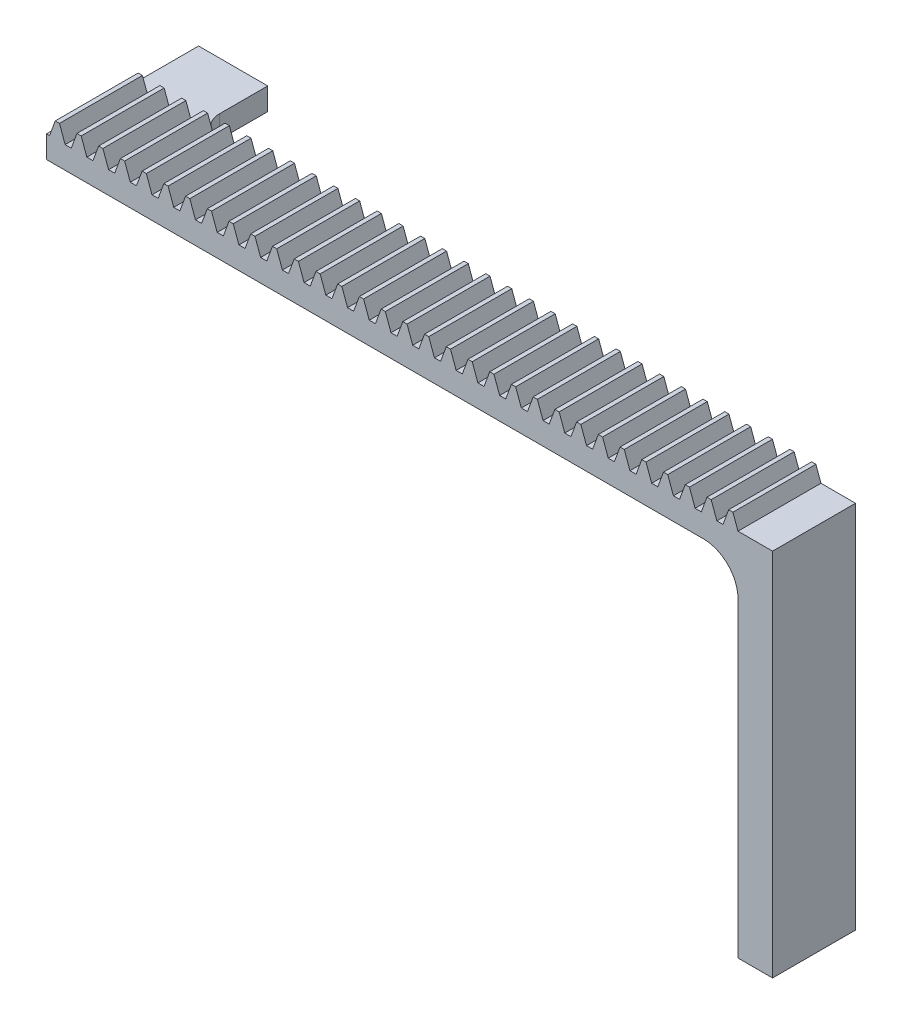
SolidWorks part; units mm, degrees
extrude "Blank" add sketch "BlankSke" against normal blind 12
sketch "BlankSke" plane through (0, 0, 0) normal (0, 0, 1) x (1, 0, 0)
  line L1 (0, 0) -> (100, 0)
  line L2 (0, 0) -> (0, 11)
  line L3 (0, 11) -> (100, 11)
  line L4 (100, 0) -> (100, 11)
  dimension "Length" = 100
ref_plane "Plane1" through (0, 0, 0) normal (0, 0, 1) x (1, 0, 0)
ref_plane "Plane2" through (0, 0, 0) normal (0, 1, 0) x (1, 0, 0)
ref_plane "Plane3" through (0, 0, 0) normal (1, 0, 0) x (0, 0, -1)
sketch "HoldingSke" plane through (0, 0, 0) normal (0, 1, 0) x (1, 0, 0)
  line L0 (0, 0) -> (0.1392, 0.9903)
  line L1 (-15, 0) -> (100, 0) construction
  line L2 (0, 0) -> (-2.1039, 2.3779)
  line L3 (0, 0) -> (-11.863, 4.5341)
  line L4 (0, 0) -> (7.2428, 4.7035)
  line L5 (0, 0) -> (-23.7986, -8.8762)
  line L6 (0, 0) -> (-10.5278, -7.1032)
  line L9 (-71.009, 38.7566) -> (22.9603, 72.9586)
  line L10 (-76.2, 3.3779) -> (-66.2, 3.3779)
  line L11 (0, 0) -> (-12, 0)
  line L12 (-76.2, 101.6) -> (-76.162, 101.6)
  line L13 (24.9733, 27.94) -> (52.9518, 28.4284)
  line L14 (24.9733, 27.94) -> (24.9743, 27.94)
  line L15 (24.9733, 27.94) -> (100.4006, 29.5858)
  circle A0 centre (0, 0) radius 19.05
  circle A1 centre (0, 0) radius 5
  circle A2 centre (0, 0) radius 12.7
  dimension "Num_teeth" = 33
  dimension "Width" = 12
  dimension "Length" = 100
  dimension "Pitch_height" = 10
sketch "TooCutSkeIll" plane through (0, 0, 0) normal (0, 0, 1) x (1, 0, 0)
  line L0 (-1.2538, 10.9737) -> (-0.5045, 8.9152)
  line L1 (-0.2687, 8.75) -> (0.2687, 8.75)
  line L2 (0.5045, 8.9152) -> (1.2538, 10.9737)
  line L3 (100, 11) -> (0, 11) construction
  line L4 (0, 0) -> (0, 64.897) construction
  line L5 (-13.208, 10) -> (12.954, 10) construction
  line L6 (0, 0) -> (100, 0) construction
  line L7 (0.8994, 10) -> (0.8994, 48.7463) construction
  line L8 (-0.8994, 10) -> (-0.8994, 48.7463) construction
  line L9 (1.2914, 11) -> (1.2914, 11.0254)
  line L10 (-1.2914, 11) -> (-1.2914, 11.0254)
  line L11 (-1.2914, 11.0254) -> (1.2914, 11.0254)
  arc A0 (0.2687, 8.75) -> (0.5045, 8.9152) centre (0.2687, 9.001) ccw
  arc A1 (-0.5045, 8.9152) -> (-0.2687, 8.75) centre (-0.2687, 9.001) ccw
  arc A2 (1.2914, 11) -> (1.2538, 10.9737) centre (1.2914, 10.96) ccw
  arc A3 (-1.2538, 10.9737) -> (-1.2914, 11) centre (-1.2914, 10.96) ccw
  dimension "Addendum_plus" = 1.0254
  dimension "Pitch_height" = 10
  dimension "Pressure_angle" = 20
  dimension "Gap_width" = 1.7988
  dimension "Dedendum" = 1.25
extrude "ToothCutIll" [suppressed] cut sketch "TooCutSkeIll" against normal through all
sketch "TooCutSkeSim" plane through (0, 0, 0) normal (0, 0, 1) x (1, 0, 0)
  line L0 (0.4444, 8.75) -> (-0.4444, 8.75)
  line L1 (1.2726, 11.0254) -> (0.4444, 8.75)
  line L2 (0, 17.4625) -> (0, 53.467) construction
  line L3 (1.2726, 11.0254) -> (-1.2726, 11.0254)
  line L6 (-1.2726, 11.0254) -> (-0.4444, 8.75)
  line L9 (-0.8994, 10) -> (0.8994, 10) construction
  line L10 (0, 0) -> (100, 0) construction
  line L11 (0.8994, 10) -> (0.8994, 53.467) construction
  line L12 (-0.8994, 10) -> (-0.8994, 53.467) construction
  dimension "Addendum_plus" = 1.0254
  dimension "Pitch_height" = 10
  dimension "Pressure_angle" = 20
  dimension "Gap_width" = 1.7988
  dimension "Dedendum" = 1.25
extrude "ToothCutSim" cut sketch "TooCutSkeSim" against normal through all
pattern_linear "TeethCuts" count 33 spacing 3.1416 along (1, 0, 0) of "ToothCutIll", "ToothCutSim"
sketch "Sketch1" plane through (100, 0, 0) normal (1, 0, 0) x (0, 0, -1)
  line L1 (0, 0) -> (12, 0)
  line L2 (0, 0) -> (0, 5.53)
  line L3 (0, 5.53) -> (12, 5.53)
  line L4 (12, 0) -> (12, 5.53)
  dimension "D1" = 5.53
extrude "Cut-Extrude1" cut sketch "Sketch1" against normal blind 126
sketch "Sketch2" plane through (100, 0, 0) normal (1, 0, 0) x (0, 0, -1)
  line L0 (12, 5.53) -> (12, 8.9877) construction
  line L1 (0, 5.53) -> (12, 5.53)
  line L2 (0, 5.53) -> (0, 8.9877)
  line L3 (0, 8.9877) -> (12, 8.9877)
  line L4 (12, 5.53) -> (12, 8.9877)
  line L6 (0, 8.9877) -> (12, 8.9877) construction
extrude "Boss-Extrude1" add sketch "Sketch2" along normal blind 5
sketch "Sketch3" plane through (0, 5.53, 0) normal (0, -1, 0) x (1, 0, 0)
  line L0 (0, -12) -> (105, -12) construction
  line L1 (105, 0) -> (100, 0)
  line L2 (105, 0) -> (105, -12)
  line L3 (105, -12) -> (100, -12)
  line L4 (100, 0) -> (100, -12)
  dimension "D1" = 5
extrude "Boss-Extrude2" add sketch "Sketch3" along normal blind 50
fillet "Fillet1" radius 5 1 edges at (100, 5.53, -6)
sketch "Sketch4" plane through (0, 0, -12) normal (0, 0, -1) x (-1, 0, 0)
  line L1 (0, 5.53) -> (-10, 5.53)
  line L2 (0, 5.53) -> (0, 8.75)
  line L3 (0, 8.75) -> (-10, 8.75)
  line L4 (-10, 5.53) -> (-10, 8.75)
  dimension "D1" = 10
extrude "Boss-Extrude3" add sketch "Sketch4" along normal blind 10
fillet "Fillet2" radius 3 1 edges at (10, 7.14, -12)
equation "' \"Module@HoldingSke\" = 6.35"
equation "' \"Num_teeth@HoldingSke\" = 12"
equation "' \"Ap@HoldingSke\" =  20"
equation "' \"Ap@HoldingSke\" = 20"
equation "' \"Width@HoldingSke\" = 0.25 * 25.4"
equation "' \"Show_teeth@HoldingSke\" = 500"
equation "' \"Backlash@HoldingSke\" = 0.009 * 25.4"
equation "' \"Addendum_fac@HoldingSke\" = 1.0"
equation "' \"Dedendum_fac@HoldingSke\" = 1.25"
equation "' \"Dedendum_add@HoldingSke\" = 0.00005 * 25.4"
equation "' \"Clearance_fac@HoldingSke\" = 0.25"
equation "' \"Pitch_height@HoldingSke\" = 1 * 25.4"
equation "' \"Length@HoldingSke\" = 4.71 * 25.4"
equation "\"Pitch@HoldingSke\" = 1 / \"Module@HoldingSke\""
equation "\"MPH@HoldingSke\" = \"Dedendum_fac@HoldingSke\" / \"Pitch@HoldingSke\" + 2 * \"Dedendum_add@HoldingSke\" + 0.002 * 25.4"
equation "\"MPH@HoldingSke\" = ((sgn( \"MPH@HoldingSke\" - \"Pitch_height@HoldingSke\")+1)*( \"MPH@HoldingSke\" - \"Pitch_height@HoldingSke\"))/2 + \"Pitch_height@HoldingSke\""
equation "\"Blank_height@BlankSke\" = \"Pitch_height@HoldingSke\" + \"Addendum_fac@HoldingSke\"  / \"Pitch@HoldingSke\" "
equation "\"Length@BlankSke\" =  \"Length@HoldingSke\""
equation "\"Face_width@Blank\" = \"Width@HoldingSke\""
equation "\"Pressure_angle@TooCutSkeIll\" = \"Ap@HoldingSke\""
equation "\"Addendum_plus@TooCutSkeIll\" =  \"Addendum_fac@HoldingSke\"  / \"Pitch@HoldingSke\" + 0.001 *25.4"
equation "\"Dedendum@TooCutSkeIll\" = \"Dedendum_fac@HoldingSke\"  / \"Pitch@HoldingSke\""
equation "\"Pitch_height@TooCutSkeIll\" =  \"MPH@HoldingSke\""
equation "\"Gap_width@TooCutSkeIll\" = 3.14159265 / 2 / \"Pitch@HoldingSke\" + 6 * \"Backlash@HoldingSke\""
equation "\"Pressure_angle@TooCutSkeSim\" = \"Ap@HoldingSke\""
equation "\"Addendum_plus@TooCutSkeSim\" =  \"Addendum_fac@HoldingSke\"  / \"Pitch@HoldingSke\" + 0.001 * 25.4"
equation "\"Dedendum@TooCutSkeSim\" = \"Dedendum_fac@HoldingSke\"  / \"Pitch@HoldingSke\""
equation "\"Pitch_height@TooCutSkeSim\" =  \"MPH@HoldingSke\""
equation "\"Gap_width@TooCutSkeSim\" = 3.14159265 / 2 / \"Pitch@HoldingSke\" + 6 * \"Backlash@HoldingSke\""
equation "\"Root_fillet@TooCutSkeIll\" = \"Clearance_fac@HoldingSke\" / \"Pitch@HoldingSke\" + \"Dedendum_add@HoldingSke\""
equation "\"Break_rad@TooCutSkeIll\" = 0.02 / \"Pitch@HoldingSke\" * 2"
equation "\"Linear_pitch@TeethCuts\" = 3.14159265 / \"Pitch@HoldingSke\""
equation "\"Num_teeth@HoldingSke\" = int( ( \"Length@HoldingSke\" + 0 ) / (3.14159265 / \"Pitch@HoldingSke\")) + 0.9999  + 1"
equation " \"Num_teeth@TeethCuts\" = int( \"Show_teeth@HoldingSke\" ) + 1"
equation " \"Num_teeth@TeethCuts\" = ((sgn( \"Num_teeth@TeethCuts\" - \"Num_teeth@HoldingSke\" )-1)*( \"Num_teeth@TeethCuts\" - \"Num_teeth@HoldingSke\" ))/-2+ \"Num_teeth@HoldingSke\""
equation " \"Num_teeth@TeethCuts\" = ((sgn( \"Num_teeth@TeethCuts\" - 2.0)+1)*( \"Num_teeth@TeethCuts\" - 2.0))/2 +2.0"
